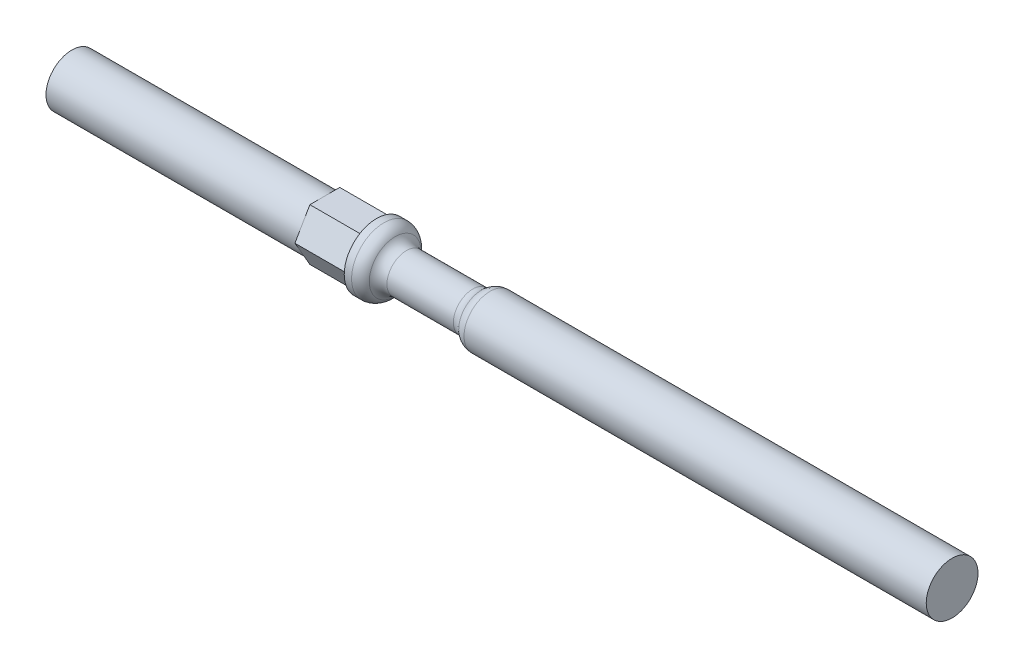
SolidWorks part; units mm, degrees
material "ABS"
ref_plane "Front Plane" through (0, 0, 0) normal (0, 0, 1) x (1, 0, 0)
ref_plane "Top Plane" through (0, 0, 0) normal (0, 1, 0) x (1, 0, 0)
ref_plane "Right Plane" through (0, 0, 0) normal (1, 0, 0) x (0, 0, -1)
sketch "Sketch1" plane through (0, 0, 0) normal (1, 0, 0) x (0, 0, -1)
  circle A0 centre (0, 0) radius 2.54
  dimension "D1" = 5.08
extrude "Boss-Extrude1" add sketch "Sketch1" along normal blind 86.36 contours A0
ref_plane "Plane1" through (29.8958, 0, 0) normal (-1, 0, 0) x (0, 0, 1)
sketch "Sketch2" plane through (29.8958, 0, 0) normal (-1, 0, 0) x (0, 0, 1)
  line L1 (2.9329, 0) -> (1.4665, 2.54)
  line L2 (1.4665, 2.54) -> (-1.4665, 2.54)
  line L3 (-1.4665, 2.54) -> (-2.9329, 0)
  line L4 (-2.9329, 0) -> (-1.4665, -2.54)
  line L5 (-1.4665, -2.54) -> (1.4665, -2.54)
  line L6 (1.4665, -2.54) -> (2.9329, 0)
  circle A0 centre (0, 0) radius 2.54 construction
  dimension "D1" = 5.08
extrude "Boss-Extrude2" add sketch "Sketch2" along normal blind 5.08
sketch "Sketch3" plane through (29.8958, 0, 0) normal (1, 0, 0) x (0, 0, -1)
  circle A0 centre (0, 0) radius 3.175
  dimension "D1" = 6.35
extrude "Boss-Extrude3" add sketch "Sketch3" along normal blind 1.651
sketch "Sketch4" plane through (31.5468, 0, 0) normal (1, 0, 0) x (0, 0, -1)
  circle A0 centre (0, 0) radius 1.905
  circle A1 centre (0, 0) radius 3.175
  circle A2 centre (0, 0) radius 3.175
  dimension "D2" = 3.81
  dimension "D1" = 0
extrude "Cut-Extrude1" cut sketch "Sketch4" along normal blind 8.89
fillet "Fillet1" radius 1.27 2 edges at (40.4368, 0, -1.905) (31.5468, 0, -1.905)
fillet "Fillet2" radius 1.27 2 edges at (31.5468, 0, -3.175) (40.4368, 0, -2.54)
